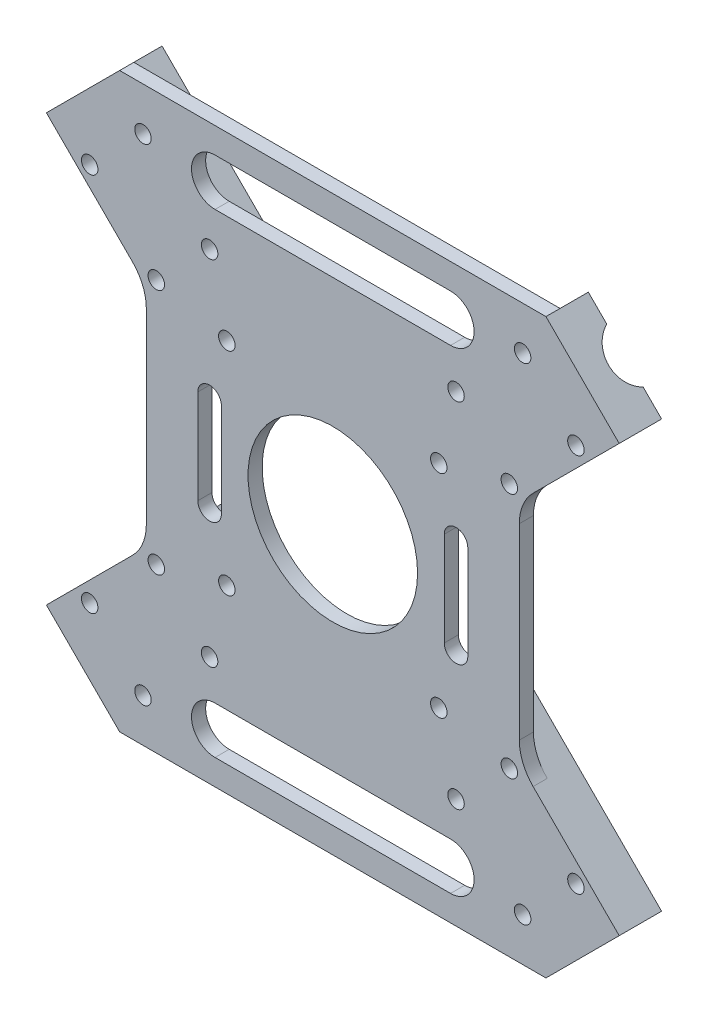
SolidWorks part; units mm, degrees
ref_plane "Front Plane" through (0, 0, 0) normal (0, 0, 1) x (1, 0, 0)
ref_plane "Top Plane" through (0, 0, 0) normal (0, 1, 0) x (1, 0, 0)
ref_plane "Right Plane" through (0, 0, 0) normal (1, 0, 0) x (0, 0, -1)
sketch "Sketch1" plane through (0, 0, 0) normal (0, 0, 1) x (1, 0, 0)
  line L0 (-45.2548, 60.8112) -> (45.2548, 60.8112)
  line L5 (-31.8198, -31.8198) -> (-45.9619, -45.9619) construction
  line L6 (0, 0) -> (0, 39.9609) construction
  line L13 (0, 0) -> (0, -32.9246) construction
  line L14 (-31.8198, -31.8198) -> (-26.163, -37.4767) construction
  line L15 (0, 0) -> (0, 22.5) construction
  line L16 (0, 0) -> (-73.0115, -73.0115) construction
  line L22 (-42.5269, -26.9706) -> (-60.8112, -45.2548)
  line L24 (-40.3051, -51.6188) -> (-51.6188, -40.3051) construction
  line L25 (-31.8198, -31.8198) -> (-37.4767, -26.163) construction
  line L26 (0, 22.5) -> (22.5, 22.5) construction
  line L27 (-24.0416, -39.598) -> (-45.2548, -60.8112)
  line L28 (-45.2548, -60.8112) -> (-60.8112, -45.2548)
  line L31 (51.6188, 40.3051) -> (40.3051, 51.6188) construction
  line L32 (0, 0) -> (-72.4223, 72.4223) construction
  line L39 (0, 0) -> (77.7251, -77.7251) construction
  line L41 (31.8198, 31.8198) -> (37.4767, 26.163) construction
  line L45 (31.8198, 31.8198) -> (26.163, 37.4767) construction
  line L46 (31.8198, 31.8198) -> (45.9619, 45.9619) construction
  line L48 (24.0416, 39.598) -> (45.2548, 60.8112)
  line L49 (60.8112, 45.2548) -> (45.2548, 60.8112)
  line L51 (0, 0) -> (31.8198, 31.8198) construction
  line L58 (42.5269, 26.9706) -> (60.8112, 45.2548)
  line L59 (0, 0) -> (84.5807, 0) construction
  line L60 (31.8198, -31.8198) -> (45.9619, -45.9619) construction
  line L62 (31.8198, -31.8198) -> (26.163, -37.4767) construction
  line L63 (31.8198, -31.8198) -> (37.4767, -26.163) construction
  line L64 (51.6188, -40.3051) -> (40.3051, -51.6188) construction
  line L65 (42.5269, -26.9706) -> (60.8112, -45.2548)
  line L68 (-15.25, -15.25) -> (15.25, 15.25) construction
  line L69 (-15.25, 15.25) -> (15.25, -15.25) construction
  line L70 (-45.2548, -60.8112) -> (45.2548, -60.8112)
  line L71 (-39.598, 19.8995) -> (-39.598, -19.8995)
  line L72 (39.598, 19.8995) -> (39.598, -19.8995)
  line L73 (0, 39.9609) -> (0, 60.8112) construction
  line L74 (-25, -55.386) -> (25, -55.386)
  line L77 (-31.8198, 31.8198) -> (-31.8198, -31.8198) construction
  line L82 (-31.8198, -31.8198) -> (31.8198, -31.8198) construction
  line L83 (31.8198, -31.8198) -> (31.8198, 31.8198) construction
  line L90 (-12.1213, -31.8198) -> (12.1213, -31.8198)
  line L95 (31.8198, -15.25) -> (31.8198, 15.25)
  line L96 (60.8112, -45.2548) -> (45.2548, -60.8112)
  line L102 (24.0416, -39.598) -> (45.2548, -60.8112)
  line L103 (22.5, 22.5) -> (22.5, -22.5) construction
  line L104 (22.5, -22.5) -> (-22.5, -22.5) construction
  line L105 (-31.8198, 31.8198) -> (-37.4767, 26.163) construction
  line L106 (-40.3051, 51.6188) -> (-51.6188, 40.3051) construction
  line L107 (-31.8198, 31.8198) -> (-26.163, 37.4767) construction
  line L108 (-31.8198, 31.8198) -> (-45.9619, 45.9619) construction
  line L109 (-22.5, -22.5) -> (-22.5, 22.5) construction
  line L110 (-22.5, 22.5) -> (0, 22.5) construction
  line L111 (-45.2548, 60.8112) -> (-60.8112, 45.2548)
  line L112 (-24.0416, 39.598) -> (-45.2548, 60.8112)
  line L113 (-42.5269, 26.9706) -> (-60.8112, 45.2548)
  line L116 (31.8198, 31.8198) -> (38.8909, 38.8909) construction
  line L119 (23.663, -10) -> (23.663, 10)
  line L123 (28.663, -10) -> (28.663, 10)
  line L124 (0, 0) -> (66.0317, 66.0317) construction
  line L125 (23.663, -10) -> (28.663, 10) construction
  line L126 (23.663, 10) -> (28.663, -10) construction
  line L127 (-28.663, -10) -> (-28.663, 10)
  line L128 (-23.663, -10) -> (-23.663, 10)
  line L130 (0, 0) -> (25, 0) construction
  line L131 (25, 0) -> (25, 40) construction
  line L132 (25, 40) -> (-25, 40) construction
  line L133 (-25, 40) -> (-25, -42) construction
  line L134 (-25, -42) -> (25, -42) construction
  line L135 (25, -42) -> (25, 0) construction
  line L138 (-25, 45.386) -> (25, 45.386)
  line L140 (-25, 55.386) -> (25, 55.386)
  line L142 (-25, 45.386) -> (25, 55.386) construction
  line L143 (-25, 55.386) -> (25, 45.386) construction
  line L144 (-25, -45.386) -> (25, -45.386)
  circle A21 centre (0, 0) radius 18
  circle A22 centre (-37.4767, -26.163) radius 1.75
  circle A23 centre (-26.163, -37.4767) radius 1.75
  circle A24 centre (-40.3051, -51.6188) radius 1.75
  circle A25 centre (-51.6188, -40.3051) radius 1.75
  circle A28 centre (-22.5, 22.5) radius 1.75
  circle A29 centre (22.5, 22.5) radius 1.75
  circle A30 centre (26.163, 37.4767) radius 1.75
  circle A31 centre (37.4767, 26.163) radius 1.75
  circle A32 centre (51.6188, 40.3051) radius 1.75
  circle A33 centre (40.3051, 51.6188) radius 1.75
  circle A34 centre (22.5, -22.5) radius 1.75
  circle A35 centre (40.3051, -51.6188) radius 1.75
  circle A36 centre (51.6188, -40.3051) radius 1.75
  circle A37 centre (37.4767, -26.163) radius 1.75
  circle A38 centre (26.163, -37.4767) radius 1.75
  circle A39 centre (-22.5, -22.5) radius 1.75
  arc A40 (39.598, 19.8995) -> (42.5269, 26.9706) centre (49.598, 19.8995) cw
  arc A41 (39.598, -19.8995) -> (42.5269, -26.9706) centre (49.598, -19.8995) ccw
  circle A42 centre (-51.6188, 40.3051) radius 1.75
  circle A43 centre (-40.3051, 51.6188) radius 1.75
  circle A44 centre (-26.163, 37.4767) radius 1.75
  circle A45 centre (-37.4767, 26.163) radius 1.75
  arc A46 (-39.598, -19.8995) -> (-42.5269, -26.9706) centre (-49.598, -19.8995) cw
  arc A47 (-39.598, 19.8995) -> (-42.5269, 26.9706) centre (-49.598, 19.8995) ccw
  arc A54 (25, 55.386) -> (25, 45.386) centre (25, 50.386) cw
  arc A56 (-25, 55.386) -> (-25, 45.386) centre (-25, 50.386) ccw
  arc A58 (-25, -55.386) -> (-25, -45.386) centre (-25, -50.386) cw
  arc A59 (25, -55.386) -> (25, -45.386) centre (25, -50.386) ccw
  arc A60 (-28.663, 10) -> (-23.663, 10) centre (-26.163, 10) cw
  arc A62 (-28.663, -10) -> (-23.663, -10) centre (-26.163, -10) ccw
  arc A63 (23.663, 10) -> (28.663, 10) centre (26.163, 10) cw
  arc A64 (23.663, -10) -> (28.663, -10) centre (26.163, -10) ccw
  point P0 (0, 0)
  point P16 (39.598, 24.0416)
  point P42 (39.598, -24.0416)
  point P51 (-39.598, -24.0416)
  point P67 (-39.598, 24.0416)
  point P79 (0, 50.386)
  point P89 (0, 50.386)
  point P106 (26.163, 0)
  dimension "D1" = 10
extrude "Boss-Extrude1" add sketch "Sketch1" along normal blind 3 contours A47 L71 A46 L22 L28 L70 L96 L65 A41 L72 A40 L58 L49 L0 L111 L113 A44 A42 A39 A38 A37 A36 A35 A34 A32 A30 region at (0, 59.0912, 0)
sketch "Sketch3" plane through (0, 0, 0) normal (0, 0, 1) x (1, 0, 0)
  line L0 (-60.8112, 45.2548) -> (-45.2548, 60.8112)
  line L1 (-45.2548, 60.8112) -> (-17.0532, 32.6096)
  line L2 (-60.8112, 45.2548) -> (-32.6096, 17.0532)
  line L3 (-32.6096, 17.0532) -> (-17.0532, 32.6096)
  line L4 (55, 0) -> (-55, 0) construction
  line L5 (-60.8112, -45.2548) -> (-32.6096, -17.0532)
  line L6 (-60.8112, -45.2548) -> (-45.2548, -60.8112)
  line L7 (-45.2548, -60.8112) -> (-17.0532, -32.6096)
  line L8 (-32.6096, -17.0532) -> (-17.0532, -32.6096)
  line L9 (0, -55) -> (0, 55) construction
  line L10 (60.8112, -45.2548) -> (45.2548, -60.8112)
  line L11 (45.2548, -60.8112) -> (17.0532, -32.6096)
  line L12 (32.6096, -17.0532) -> (17.0532, -32.6096)
  line L13 (60.8112, -45.2548) -> (32.6096, -17.0532)
  line L14 (60.8112, 45.2548) -> (32.6096, 17.0532)
  line L15 (60.8112, 45.2548) -> (45.2548, 60.8112)
  line L16 (45.2548, 60.8112) -> (17.0532, 32.6096)
  line L17 (32.6096, 17.0532) -> (17.0532, 32.6096)
extrude "Boss-Extrude3" add sketch "Sketch3" against normal blind 6
sketch "Sketch4" plane through (-53.033, 53.033, 0) normal (-0.7071, 0.7071, 0) x (0, 0, 1)
  line L0 (3, 0) -> (0, 0) construction
  line L1 (3, 11) -> (3, -11) construction
  line L2 (0, 0) -> (-8.5, 0) construction
  circle A0 centre (-8.5, 0) radius 6
extrude "Cut-Extrude1" cut sketch "Sketch4" against normal up to surface (150 mm away) up to face at (51.4774, -54.5886, -1.2)
sketch "Sketch5" plane through (-53.033, -53.033, 0) normal (-0.7071, -0.7071, 0) x (0, 0, 1)
  line L0 (3, 0) -> (0, 0) construction
  line L1 (3, -11) -> (3, 11) construction
  line L2 (0, 0) -> (-8.5, 0) construction
  circle A0 centre (-8.5, 0) radius 6
extrude "Cut-Extrude2" cut sketch "Sketch5" against normal up to surface (150 mm away) up to face at (51.4774, 54.5886, -1.2)
extrude "Cut-Extrude3" cut sketch "Sketch1<7>" against normal blind 12 contours A42 | A43 | A45 | A44 | A30 | A33 | A32 | A37 | A38 | A35 | A36 | A23 | A22 | A25 | A24
sketch "Sketch1<7>" plane through (0, 0, 0) normal (0, 0, 1) x (1, 0, 0) same geometry as "Sketch1"
extrude "Cut-Extrude4" cut sketch "Sketch1<8>" against normal blind 12 contours A31
sketch "Sketch1<8>" plane through (0, 0, 0) normal (0, 0, 1) x (1, 0, 0) same geometry as "Sketch1"
